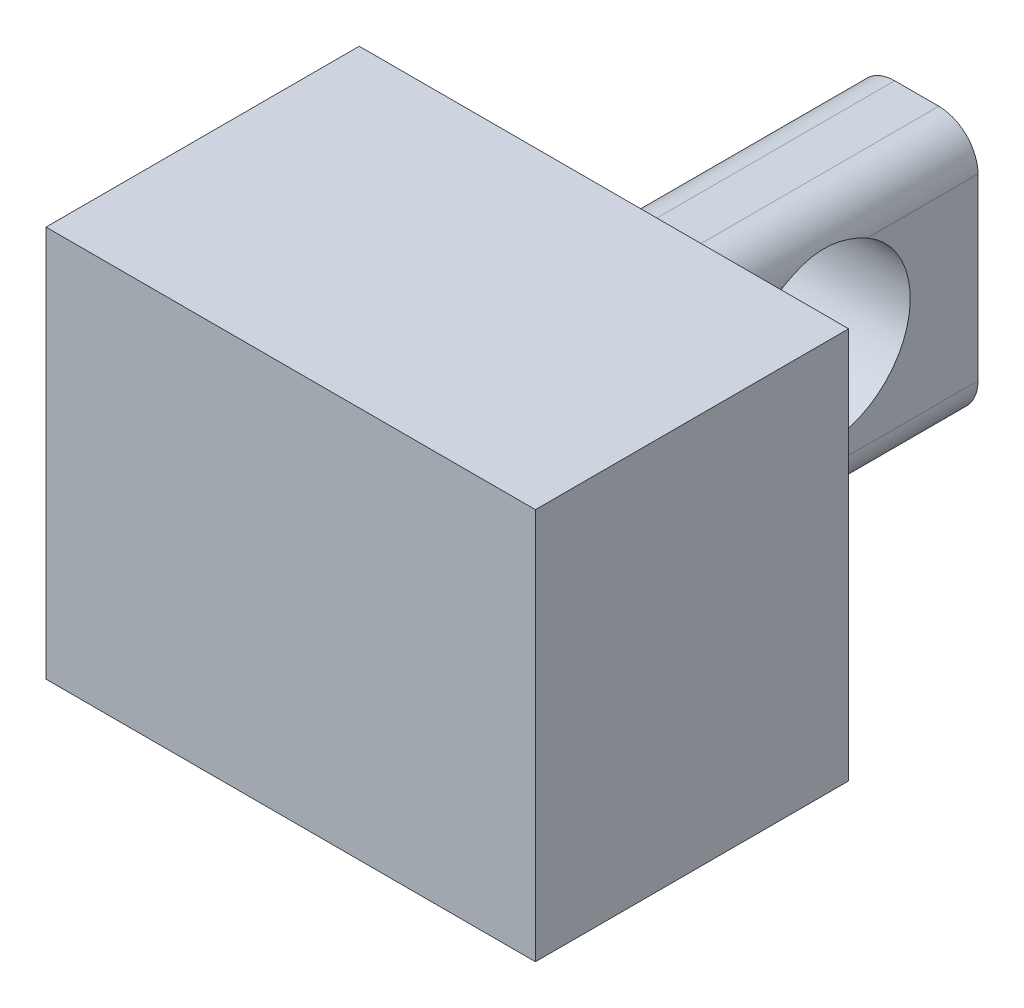
SolidWorks part; units mm, degrees
ref_plane "Front Plane" through (0, 0, 0) normal (0, 0, 1) x (1, 0, 0)
ref_plane "Top Plane" through (0, 0, 0) normal (0, 1, 0) x (1, 0, 0)
ref_plane "Right Plane" through (0, 0, 0) normal (1, 0, 0) x (0, 0, -1)
sketch "Sketch1" plane through (0, 0, 0) normal (0, 0, 1) x (1, 0, 0)
  line L1 (-26.356, -3.5079) -> (-25.106, -3.5079)
  line L2 (-26.356, -3.5079) -> (-26.356, -4.5079)
  line L3 (-26.356, -4.5079) -> (-25.106, -4.5079)
  line L4 (-25.106, -3.5079) -> (-25.106, -4.5079)
  dimension "D1" = 1
extrude "Boss-Extrude1" add sketch "Sketch1" along normal blind 0.8
sketch "Sketch2" plane through (0, 0, 0) normal (0, 0, 1) x (1, 0, 0)
  line L1 (-25.8884, -3.7004) -> (-25.5756, -3.7004)
  line L2 (-25.8884, -3.7004) -> (-25.8884, -4.3576)
  line L3 (-25.8884, -4.3576) -> (-25.5756, -4.3576)
  line L4 (-25.5756, -3.7004) -> (-25.5756, -4.3576)
extrude "Boss-Extrude3" add sketch "Sketch2" against normal blind 0.8
sketch "Sketch3" plane through (-25.5756, 0, 0) normal (1, 0, 0) x (0, 0, -1)
  circle A0 centre (0.4105, -3.989) radius 0.2164
extrude "Cut-Extrude1" cut sketch "Sketch3" against normal through all both and the other way through all
fillet "Fillet1" radius 0.1 1 edges at (-25.5756, -3.7004, -0.4)
fillet "Fillet2" radius 0.1 2 edges at (-25.8884, -3.7004, -0.4) (-25.5756, -4.3576, -0.4)
fillet "Fillet3" radius 0.1 1 edges at (-25.8884, -4.3576, -0.4)
